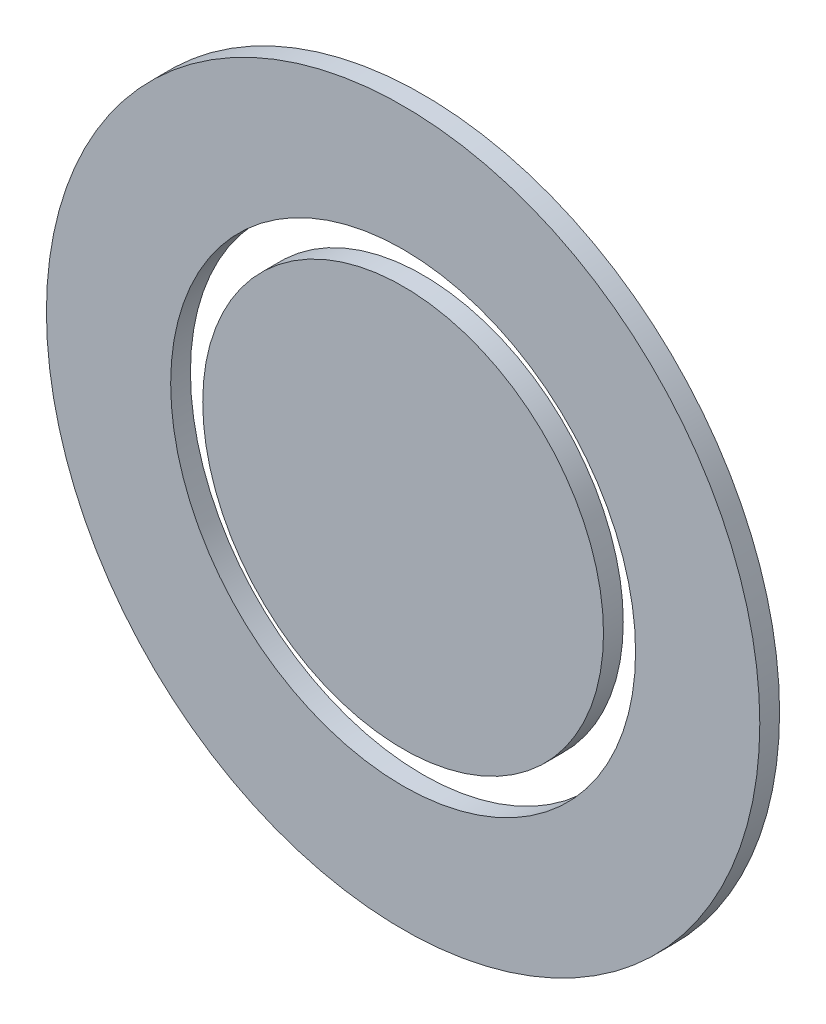
SolidWorks part; units mm, degrees
material "Bismuth"
ref_plane "Front" through (0, 0, 0) normal (0, 0, 1) x (1, 0, 0)
ref_plane "Top" through (0, 0, 0) normal (0, 1, 0) x (1, 0, 0)
ref_plane "Right" through (0, 0, 0) normal (1, 0, 0) x (0, 0, -1)
sketch "Sketch1" plane through (0, 0, 0) normal (0, 0, 1) x (1, 0, 0)
  circle A0 centre (0, 0) radius 133.5
  circle A1 centre (0, 0) radius 87
  circle A2 centre (0, 0) radius 75
extrude "Boss-Extrude1" add sketch "Sketch1" along normal blind 7.4 contours A2
extrude "Boss-Extrude2" add sketch "Sketch1<3>" along normal blind 7.4 separate body contours A0 | A1
sketch "Sketch1<3>" plane through (0, 0, 0) normal (0, 0, 1) x (1, 0, 0) same geometry as "Sketch1"
